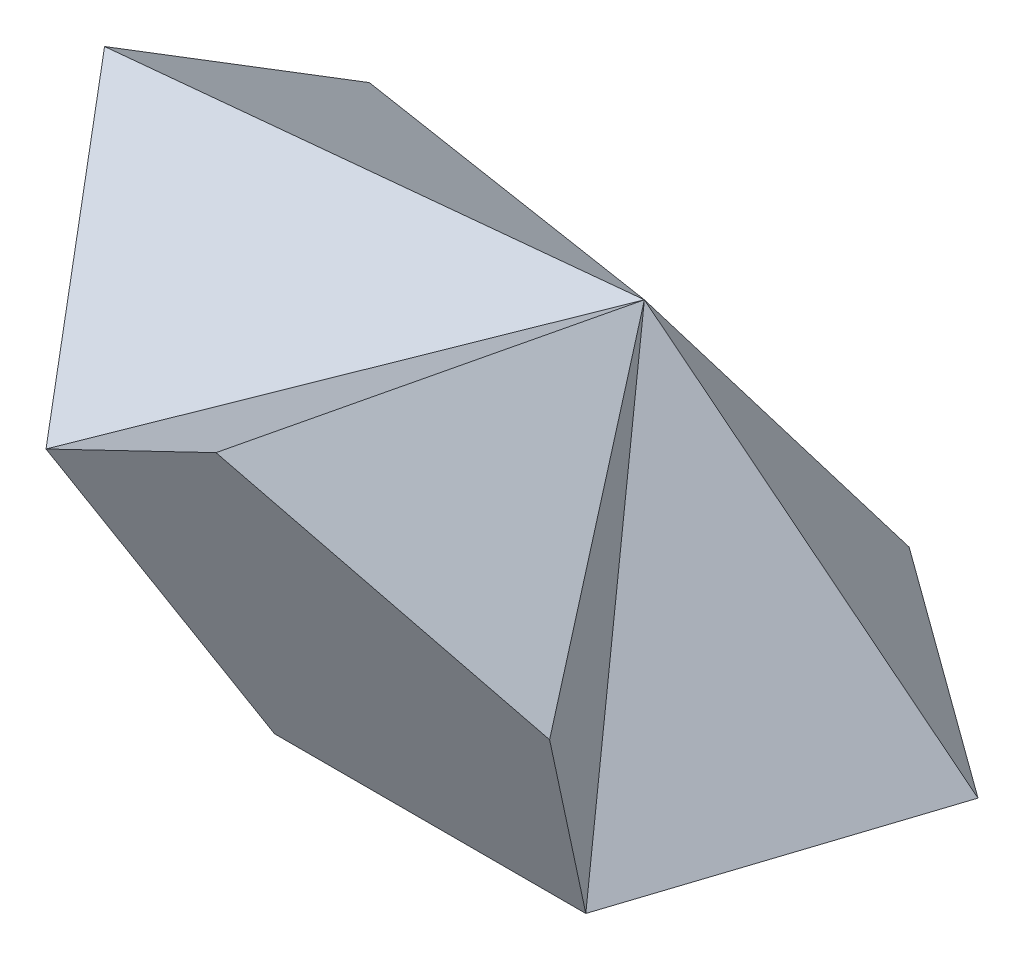
SolidWorks part; units mm, degrees
ref_plane "Front Plane" through (0, 0, 0) normal (0, 0, 1) x (1, 0, 0)
ref_plane "Top Plane" through (0, 0, 0) normal (0, 1, 0) x (1, 0, 0)
ref_plane "Right Plane" through (0, 0, 0) normal (1, 0, 0) x (0, 0, -1)
sketch "Sketch1" plane through (0, 0, 0) normal (0, 1, 0) x (1, 0, 0)
  line L1 (0, 10.8033) -> (-10.2745, 3.3384)
  line L2 (-10.2745, 3.3384) -> (-6.35, -8.74)
  line L3 (-6.35, -8.74) -> (6.35, -8.74)
  line L4 (6.35, -8.74) -> (10.2745, 3.3384)
  line L5 (10.2745, 3.3384) -> (0, 10.8033)
  circle A0 centre (0, 0) radius 8.74 construction
  dimension "D1" = 12.7
extrude "Boss-Extrude1" add sketch "Sketch1" along normal blind 25.4 draft 31.717
mirror "Mirror1" [suppressed]
mirror "Mirror2" about plane through (-6.35, 0, 8.74) normal (0, 0.5257, 0.8507) of "Boss-Extrude1"
mirror "Mirror3" about plane through (-10.2745, 0, -3.3384) normal (-0.809, 0.5257, 0.2629) of "Boss-Extrude1"
equation "\"angle\"= arccos ( - sqr ( 5 ) / 5 )"
equation "\"theta\"= 90 - \"angle\" / 2"
equation "\"side\"=0.5"
equation "\"D1@Sketch1\"=\"side\""
equation "\"D3@Boss-Extrude1\"=\"theta\""
equation "\"D1@Boss-Extrude1\"=\"side\"*2"
